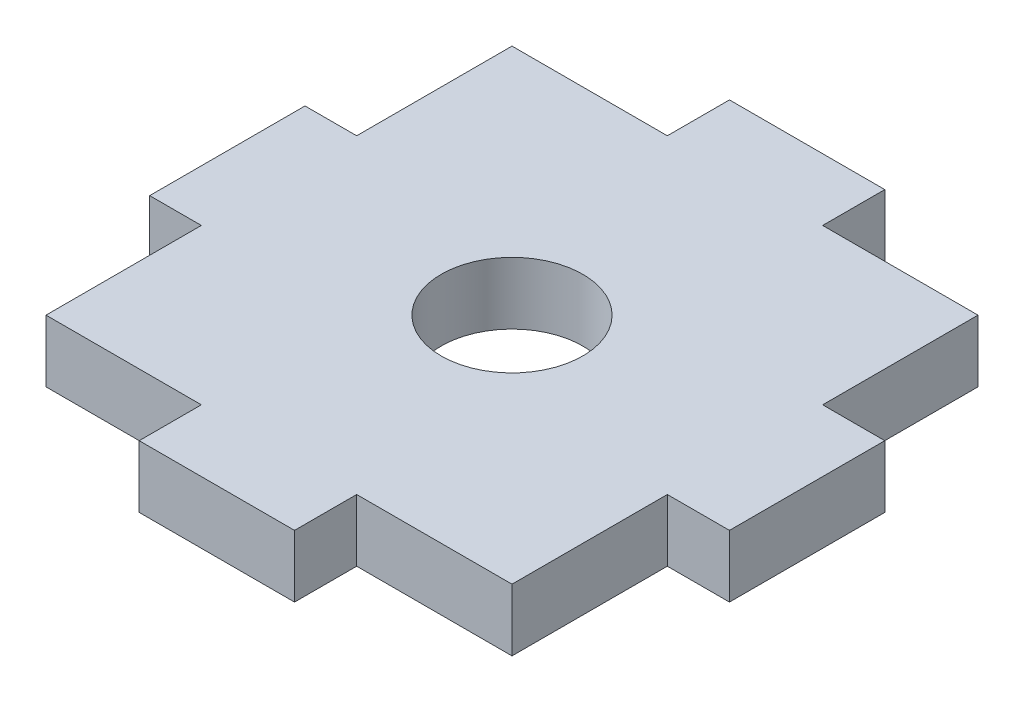
SolidWorks part; units mm, degrees
ref_plane "Front Plane" through (0, 0, 0) normal (0, 0, 1) x (1, 0, 0)
ref_plane "Top Plane" through (0, 0, 0) normal (0, 1, 0) x (1, 0, 0)
ref_plane "Right Plane" through (0, 0, 0) normal (1, 0, 0) x (0, 0, -1)
other "Configuration Table"
sketch "Sketch1" plane through (0, 0, 0) normal (0, 1, 0) x (1, 0, 0)
  line L23 (-23.3832, -3.008) -> (-23.3832, -41.008) construction
  line L40 (-41.7087, -22.008) -> (-4.3832, -22.008) construction
  line L77 (-28.3832, -37.008) -> (-28.3832, -41.008)
  line L78 (-28.3832, -41.008) -> (-18.3832, -41.008)
  line L79 (-18.3832, -37.008) -> (-18.3832, -41.008)
  line L90 (-28.3832, -3.008) -> (-18.3832, -3.008)
  line L91 (-28.3832, -3.008) -> (-28.3832, -7.008)
  line L93 (-18.3832, -3.008) -> (-18.3832, -7.008)
  line L98 (-41.7087, -17.008) -> (-38.3832, -17.008)
  line L99 (-41.7087, -17.008) -> (-41.7087, -27.008)
  line L100 (-41.7087, -27.008) -> (-38.3832, -27.008)
  line L102 (-38.3832, -17.008) -> (-38.3832, -7.008)
  line L103 (-38.3832, -27.008) -> (-38.3832, -37.008)
  line L104 (-38.3832, -37.008) -> (-28.3832, -37.008)
  line L105 (-18.3832, -37.008) -> (-8.3832, -37.008)
  line L111 (-8.3832, -17.008) -> (-4.3832, -17.008)
  line L113 (-8.3832, -27.008) -> (-4.3832, -27.008)
  line L114 (-4.3832, -17.008) -> (-4.3832, -27.008)
  line L116 (-38.3832, -7.008) -> (-28.3832, -7.008)
  line L117 (-18.3832, -7.008) -> (-8.3832, -7.008)
  line L119 (-8.3832, -7.008) -> (-8.3832, -17.008)
  line L120 (-8.3832, -27.008) -> (-8.3832, -37.008)
  circle A0 centre (-23.3832, -22.008) radius 4.5577
  point P0 (0, 0)
  dimension "D1" = 37.3255
  dimension "D2" = 10
  dimension "D3" = 20
  dimension "D4" = 30
  dimension "D5" = 20
  dimension "D6" = 10
  dimension "D7" = 30
  dimension "D8" = 10
  dimension "D9" = 10
  dimension "D10" = 10
  dimension "D11" = 30
  dimension "D12" = 30
  dimension "D13" = 30
  dimension "D14" = 10
  dimension "D15" = 10
extrude "Boss-Extrude1" add sketch "Sketch1" along normal blind 4
